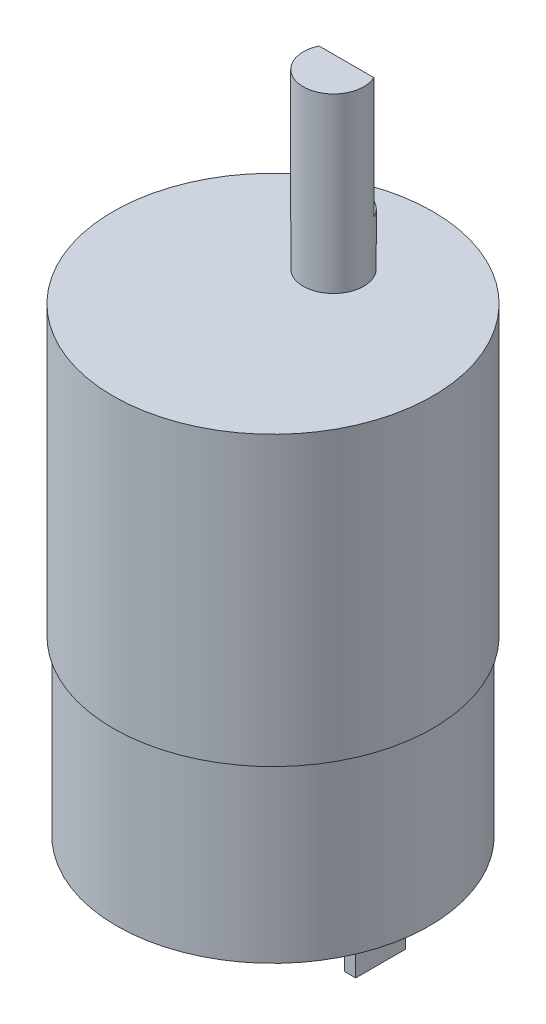
SolidWorks part; units mm, degrees
ref_plane "Front Plane" through (0, 0, 0) normal (0, 0, 1) x (1, 0, 0)
ref_plane "Top Plane" through (0, 0, 0) normal (0, 1, 0) x (1, 0, 0)
ref_plane "Right Plane" through (0, 0, 0) normal (1, 0, 0) x (0, 0, -1)
sketch "Sketch1" plane through (0, 0, 0) normal (0, 1, 0) x (1, 0, 0)
  circle A0 centre (0, 0) radius 18.1
  dimension "D1" = 36.2
extrude "Boss-Extrude1" add sketch "Sketch1" along normal blind 20
sketch "Sketch2" plane through (0, 20, 0) normal (0, 1, 0) x (1, 0, 0)
  circle A0 centre (0, 0) radius 18.5
  dimension "D1" = 37
extrude "Boss-Extrude2" add sketch "Sketch2" along normal blind 33.3
sketch "Sketch3" plane through (0, 0, 0) normal (0, -1, 0) x (1, 0, 0)
  circle A0 centre (0, 0) radius 4.6664
extrude "Boss-Extrude3" add sketch "Sketch3" along normal blind 3.81
sketch "Sketch4" plane through (0, 0, 0) normal (0, -1, 0) x (1, 0, 0)
  line L1 (-12.7, 3.1306) -> (-11.43, 3.1306)
  line L2 (-12.7, 3.1306) -> (-12.7, -2.6581)
  line L3 (-12.7, -2.6581) -> (-11.43, -2.6581)
  line L4 (-11.43, 3.1306) -> (-11.43, -2.6581)
  line L5 (11.43, 3.1306) -> (12.7, 3.1306)
  line L6 (11.43, 3.1306) -> (11.43, -2.6581)
  line L7 (11.43, -2.6581) -> (12.7, -2.6581)
  line L8 (12.7, 3.1306) -> (12.7, -2.6581)
  dimension "D1" = 1.27
  dimension "D2" = 11.43
  dimension "D3" = 11.43
extrude "Boss-Extrude4" add sketch "Sketch4" along normal blind 6.35
sketch "Sketch5" plane through (0, 53.3, 0) normal (0, 1, 0) x (1, 0, 0)
  line L0 (-9.25, 16.0215) -> (0, 0) construction
  line L1 (0, 0) -> (9.25, 16.0215) construction
  circle A0 centre (0, 7) radius 3.5
  circle A1 centre (0, 0) radius 18.5 construction
  point P8 (0, 0)
  dimension "D1" = 7
  dimension "D2" = 60
extrude "Boss-Extrude5" add sketch "Sketch5" along normal blind 20
sketch "Sketch7" plane through (0, 0, 0) normal (1, 0, 0) x (0, 0, -1)
  line L1 (10.5, 73.3) -> (8.5, 73.3)
  line L2 (10.5, 73.3) -> (10.5, 59.3)
  line L3 (10.5, 59.3) -> (8.5, 59.3)
  line L4 (8.5, 73.3) -> (8.5, 59.3)
  dimension "D1" = 14
  dimension "D2" = 2
extrude "Cut-Extrude1" cut sketch "Sketch7" against normal through all and the other way through all contours L2 L3 L4 L1
